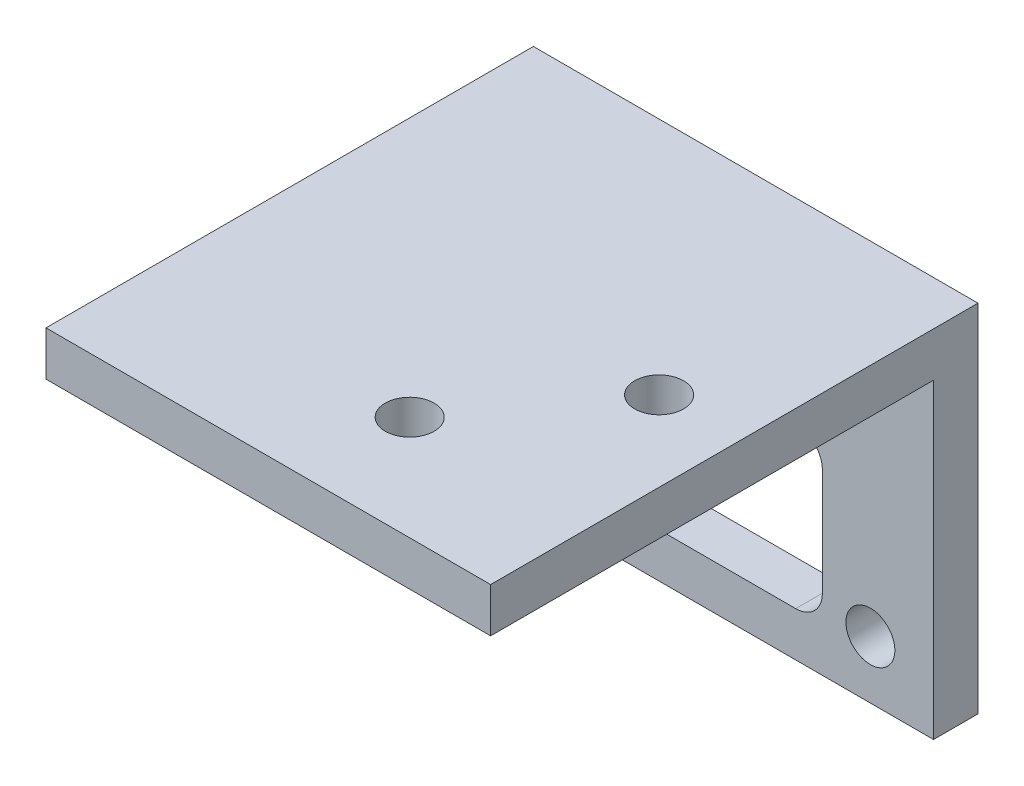
SolidWorks part; units mm, degrees
ref_plane "Front Plane" through (0, 0, 0) normal (0, 0, 1) x (1, 0, 0)
ref_plane "Top Plane" through (0, 0, 0) normal (0, 1, 0) x (1, 0, 0)
ref_plane "Right Plane" through (0, 0, 0) normal (1, 0, 0) x (0, 0, -1)
sketch "Sketch1" plane through (0, 0, 0) normal (0, 0, 1) x (1, 0, 0)
  line L0 (25, 40) -> (25, 0) construction
  line L1 (0, 0) -> (50, 0)
  line L2 (0, 0) -> (0, 40)
  line L3 (0, 40) -> (50, 40)
  line L4 (50, 0) -> (50, 40)
  line L5 (7.1, 6.5) -> (42.9, 6.5) construction
  line L6 (12.5, 23) -> (12.5, 5)
  line L9 (12.5, 23) -> (37.5, 23)
  line L10 (12.5, 5) -> (37.5, 5)
  line L11 (37.5, 23) -> (37.5, 5)
  circle A0 centre (7.1, 6.5) radius 2.75
  circle A1 centre (42.9, 6.5) radius 2.75
  circle A4 centre (15, 29.5) radius 2.75
  circle A6 centre (35, 29.5) radius 2.75
  point P9 (15.5954, 22.5506)
  point P15 (25, 5)
  point P16 (25, 23)
  dimension "D3" = 5.5
  dimension "D5" = 6.5
  dimension "D1" = 50
  dimension "D2" = 40
  dimension "D4" = 35.8
  dimension "D6" = 18
  dimension "D7" = 5
  dimension "D8" = 23
  dimension "D9" = 20
  dimension "D10" = 25
extrude "Boss-Extrude1" add sketch "Sketch1" along normal blind 5
sketch "Sketch2" plane through (0, 0, 5) normal (0, 0, 1) x (1, 0, 0)
  line L0 (0, 40) -> (0, 0) construction
  line L1 (0, 40) -> (50, 40)
  line L2 (0, 40) -> (0, 35)
  line L3 (0, 35) -> (50, 35)
  line L4 (50, 40) -> (50, 35)
  line L5 (50, 40) -> (0, 40) construction
  line L6 (50, 0) -> (50, 40) construction
  dimension "D1" = 5
extrude "Boss-Extrude2" add sketch "Sketch2" along normal blind 49.81
sketch "Sketch3" plane through (0, 35, 0) normal (0, -1, 0) x (1, 0, 0)
  line L0 (0, 54.81) -> (50, 54.81) construction
  line L2 (50, 54.81) -> (50, 5) construction
  circle A0 centre (29.15, 43.06) radius 2.75
  circle A1 centre (41, 26.86) radius 2.75
  dimension "D1" = 5.5
  dimension "D3" = 9
  dimension "D4" = 9
  dimension "D5" = 20.85
  dimension "D2" = 25.2
extrude "Cut-Extrude1" cut sketch "Sketch3" against normal up to next
fillet "Fillet1" radius 3 4 edges at (37.5, 5, 2.5) (37.5, 23, 2.5) (12.5, 23, 2.5) (12.5, 5, 2.5)
